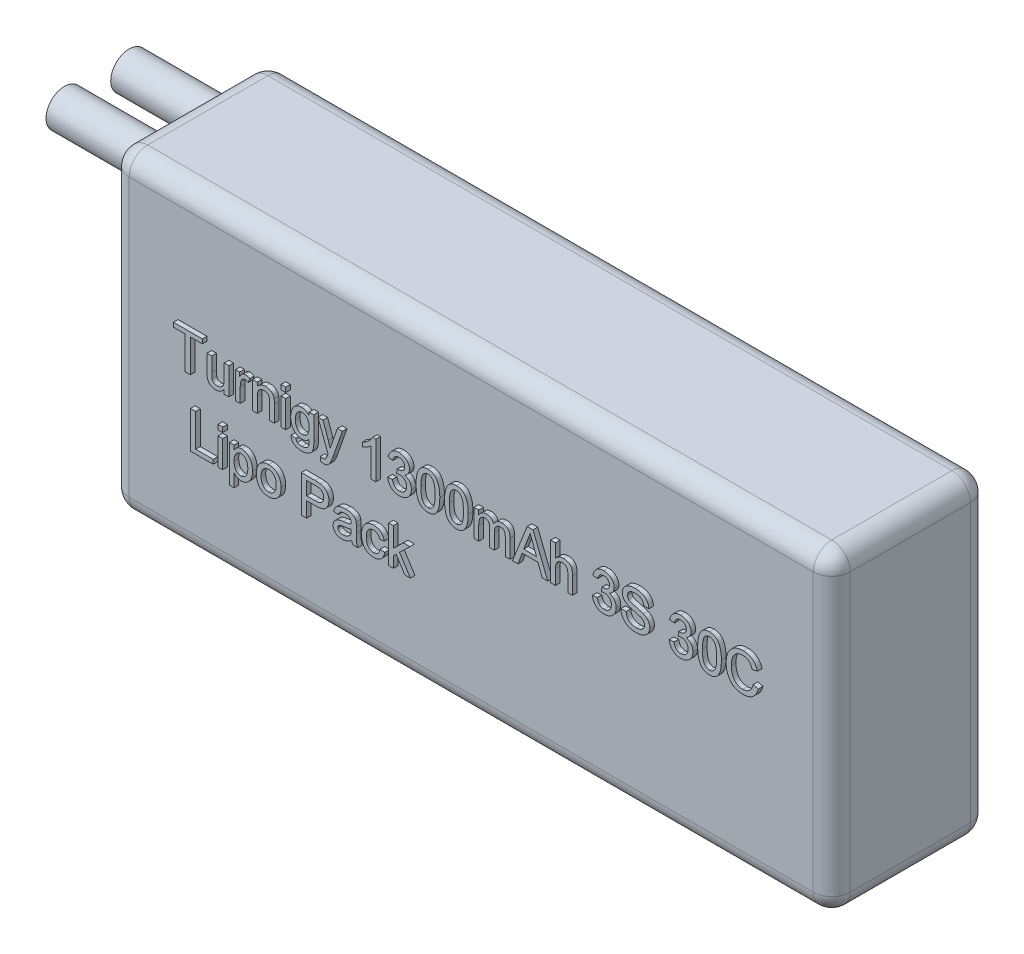
SolidWorks part; units mm, degrees
ref_plane "Спереди" through (0, 0, 0) normal (0, 0, 1) x (1, 0, 0)
ref_plane "Сверху" through (0, 0, 0) normal (0, 1, 0) x (1, 0, 0)
ref_plane "Справа" through (0, 0, 0) normal (1, 0, 0) x (0, 0, -1)
sketch "Эскиз1" plane through (0, 0, 0) normal (0, 0, 1) x (1, 0, 0)
  line L1 (-39, 17) -> (39, 17)
  line L2 (-39, 17) -> (-39, -17)
  line L3 (-39, -17) -> (39, -17)
  line L4 (39, 17) -> (39, -17)
  line L5 (-39, 17) -> (39, -17) construction
  line L6 (-39, -17) -> (39, 17) construction
  point P0 (0, 0)
  dimension "D1" = 78
  dimension "D2" = 34
extrude "Бобышка-Вытянуть1" add sketch "Эскиз1" along normal blind 17
sketch "Эскиз2" plane through (-39, 0, 0) normal (-1, 0, 0) x (0, 0, 1)
  line L0 (5, 13) -> (12, 13) construction
  line L1 (8.5, 13) -> (8.5, 17) construction
  line L2 (17, 17) -> (0, 17) construction
  circle A0 centre (5, 13) radius 2
  circle A1 centre (12, 13) radius 2
  dimension "D1" = 4
  dimension "D2" = 7
  dimension "D3" = 4
extrude "Бобышка-Вытянуть2" add sketch "Эскиз2" along normal blind 10
sketch "Эскиз3" plane through (0, 0, 17) normal (0, 0, 1) x (1, 0, 0)
  text T0 "Turnigy 1300mAh 3S 30C\r\n Lipo Pack"
extrude "Бобышка-Вытянуть3" add sketch "Эскиз3" along normal blind 0.5
fillet "Redondeo2" radius 2 12 edges at (-39, 17, 8.5) (-39, -17, 8.5) (39, 17, 8.5) (39, -17, 8.5) (39, 0, 17) (0, -17, 17) (0, 17, 17) (-39, 0, 17) (-39, 0, 0) (0, -17, 0) (39, 0, 0) (0, 17, 0)
